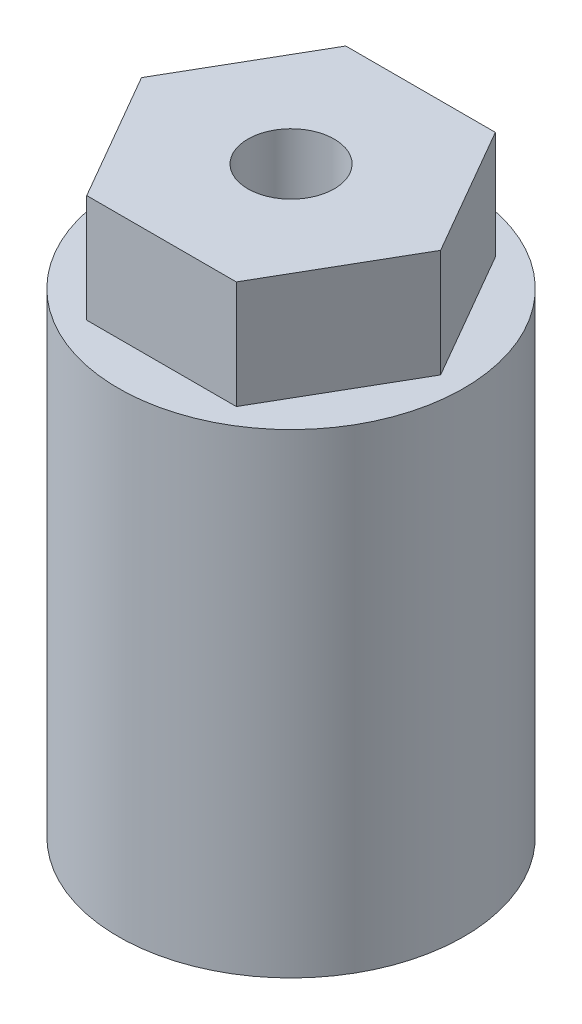
SolidWorks part; units mm, degrees
ref_plane "Front Plane" through (0, 0, 0) normal (0, 0, 1) x (1, 0, 0)
ref_plane "Top Plane" through (0, 0, 0) normal (0, 1, 0) x (1, 0, 0)
ref_plane "Right Plane" through (0, 0, 0) normal (1, 0, 0) x (0, 0, -1)
sketch "Sketch1" plane through (0, 0, 0) normal (0, 0, 1) x (1, 0, 0)
  line L0 (0, 0) -> (0, 16.2128) construction
  line L2 (0, 0) -> (8, 0)
  line L3 (0, 0) -> (0, 12)
  line L4 (0, 12) -> (8, 12)
  line L5 (8, 0) -> (8, 12)
  line L6 (0, 0) -> (4, 0)
  line L7 (0, 0) -> (0, 12)
  line L8 (0, 12) -> (4, 12)
  line L9 (4, 0) -> (4, 12)
  line L10 (8, 12) -> (0, 12)
  line L11 (8, 12) -> (8, 22)
  line L12 (8, 22) -> (0, 22)
  line L13 (0, 12) -> (0, 22)
  dimension "D1" = 12
  dimension "D2" = 4
  dimension "D3" = 4
  dimension "D4" = 10
revolve "Revolve1" add sketch "Sketch1" angle 360 about L0 region at (6, 6, 0) region at (4, 17, 0)
sketch "Sketch2" plane through (0, 22, 0) normal (0, 1, 0) x (1, 0, 0)
  line L1 (6.9282, 0) -> (3.4641, 6)
  line L2 (3.4641, 6) -> (-3.4641, 6)
  line L3 (-3.4641, 6) -> (-6.9282, 0)
  line L4 (-6.9282, 0) -> (-3.4641, -6)
  line L5 (-3.4641, -6) -> (3.4641, -6)
  line L6 (3.4641, -6) -> (6.9282, 0)
  circle A0 centre (0, 0) radius 6 construction
  dimension "D1" = 12
extrude "Boss-Extrude1" add sketch "Sketch2" along normal blind 5
hole_wizard "Ø4.0mm Dowel Hole1" positions "Sketch3" profile "Sketch4" hole size "Ø4.0" standard "ANSI Metric"
sketch "Sketch3" plane through (0, 27, 0) normal (0, 1, 0) x (1, 0, 0)
  point P0 (0, 0)
sketch "Sketch4" plane through (0, 27, 0) normal (1, 0, 0) x (0, 0, 1)
  line L0 (0, 0) -> (0, 11.2017)
  line L1 (0, 11.2017) -> (2, 10)
  line L2 (2, 10) -> (2, 0)
  line L5 (2, 0) -> (0, 0)
  line L10 (0, 11.2017) -> (-2, 10) construction
  line L11 (0, -6.35) -> (0, 107.95) construction
  dimension "Hole Dia." = 4
  dimension "Hole Depth" = 10
  dimension "Drill Angle" = 118
sketch "Sketch5" plane through (0, 0, 0) normal (0, -1, 0) x (1, 0, 0)
  line L1 (2.5, -1.5) -> (5.5, -1.5)
  line L2 (2.5, -1.5) -> (2.5, 1.5)
  line L3 (2.5, 1.5) -> (5.5, 1.5)
  line L4 (5.5, -1.5) -> (5.5, 1.5)
  line L5 (2.5, -1.5) -> (5.5, 1.5) construction
  line L6 (2.5, 1.5) -> (5.5, -1.5) construction
  circle A0 centre (0, 0) radius 4 construction
  point P0 (4, 0)
  dimension "D1" = 3
  dimension "D2" = 3
extrude "Cut-Extrude1" cut sketch "Sketch5" against normal up to surface (12 mm away) up to face at (0, 12, -4)
